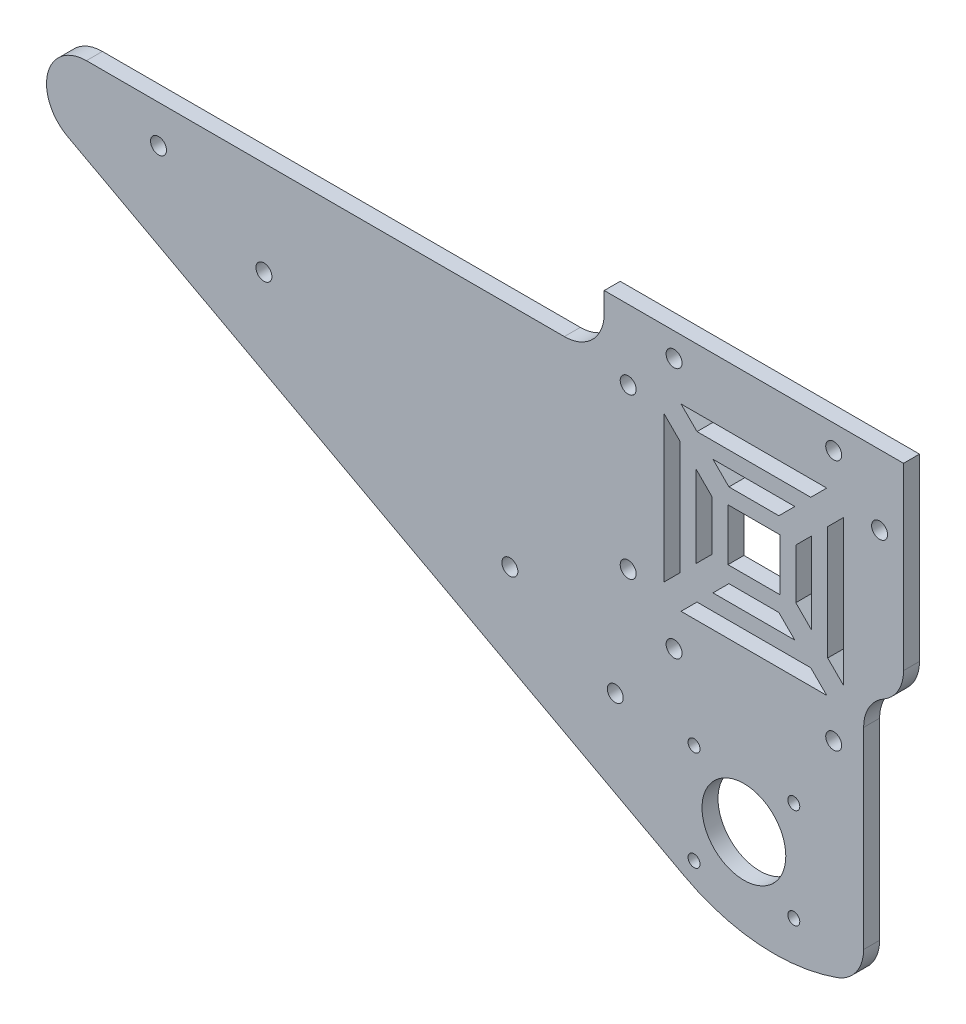
SolidWorks part; units mm, degrees
material "Thornel Mat VMA"
ref_plane "前视基准面" through (0, 0, 0) normal (0, 0, 1) x (1, 0, 0)
ref_plane "上视基准面" through (0, 0, 0) normal (0, 1, 0) x (1, 0, 0)
ref_plane "右视基准面" through (0, 0, 0) normal (1, 0, 0) x (0, 0, -1)
sketch "草图2" plane through (0, 0, 0) normal (0, 0, 1) x (1, 0, 0)
  line L0 (0, 0) -> (-75, 0)
  line L5 (-75, 0) -> (-75, -15)
  line L6 (-75, -15) -> (-244.4346, -15)
  line L7 (-244.4346, -15) -> (-55, -117)
  line L8 (-55, -117) -> (0, -117)
  line L9 (0, -117) -> (0, 0)
  dimension "D1" = 75
  dimension "D2" = 117
  dimension "D3" = 28.3
  dimension "D4" = 15
  dimension "D5" = 55
extrude "凸台-拉伸1" add sketch "草图2" along normal blind 4
sketch "草图3" plane through (0, 0, 4) normal (0, 0, 1) x (1, 0, 0)
  line L0 (-37.5, 0) -> (-37.5, -87.0707) construction
  line L1 (0, 0) -> (-75, 0) construction
  line L3 (-69, -17.5) -> (-6, -17.5) construction
  line L4 (-69, -17.5) -> (-69, -57.5) construction
  line L5 (-69, -57.5) -> (-6, -57.5) construction
  line L6 (-6, -17.5) -> (-6, -57.5) construction
  line L7 (-69, -17.5) -> (-6, -57.5) construction
  line L8 (-69, -57.5) -> (-6, -17.5) construction
  line L9 (-57.5, -6) -> (-17.5, -6) construction
  line L10 (-57.5, -6) -> (-57.5, -69) construction
  line L11 (-57.5, -69) -> (-17.5, -69) construction
  line L12 (-17.5, -6) -> (-17.5, -69) construction
  line L13 (-57.5, -6) -> (-17.5, -69) construction
  line L14 (-57.5, -69) -> (-17.5, -6) construction
  circle A0 centre (-57.5, -6) radius 2
  circle A1 centre (-69, -17.5) radius 2
  circle A2 centre (-17.5, -6) radius 2
  circle A3 centre (-6, -17.5) radius 2
  circle A4 centre (-6, -57.5) radius 2
  circle A5 centre (-17.5, -69) radius 2
  circle A6 centre (-57.5, -69) radius 2
  circle A7 centre (-69, -57.5) radius 2
  point P4 (-37.5, -37.5)
  point P9 (-37.5, -37.5)
  dimension "D6" = 4
  dimension "D1" = 63
  dimension "D2" = 40
  dimension "D3" = 37.5
  dimension "D4" = 40
  dimension "D5" = 63
extrude "切除-拉伸1" cut sketch "草图3" against normal through all
sketch "草图4" plane through (0, 0, 4) normal (0, 0, 1) x (1, 0, 0)
  line L0 (0, 0) -> (-75, 0) construction
  line L1 (0, -117) -> (0, 0) construction
  line L2 (-52.5, -87.5) -> (-27.5, -87.5) construction
  line L3 (-52.5, -87.5) -> (-52.5, -112.5) construction
  line L4 (-52.5, -112.5) -> (-27.5, -112.5) construction
  line L5 (-27.5, -87.5) -> (-27.5, -112.5) construction
  line L6 (-52.5, -87.5) -> (-27.5, -112.5) construction
  line L7 (-52.5, -112.5) -> (-27.5, -87.5) construction
  circle A0 centre (-40, -100) radius 10.5
  circle A1 centre (-52.5, -112.5) radius 1.5
  circle A2 centre (-27.5, -112.5) radius 1.5
  circle A3 centre (-27.5, -87.5) radius 1.5
  circle A4 centre (-52.5, -87.5) radius 1.5
  point P6 (-40, -100)
  dimension "D1" = 21
  dimension "D6" = 3
  dimension "D2" = 100
  dimension "D3" = 40
  dimension "D4" = 25
  dimension "D5" = 25
extrude "切除-拉伸2" cut sketch "草图4" against normal through all
sketch "草图5" plane through (0, 0, 4) normal (0, 0, 1) x (1, 0, 0)
  line L0 (-14.7555, -117) -> (-204.1901, -15) construction
  line L3 (-55, -117) -> (0, -117) construction
  line L4 (-75, -15) -> (-244.4346, -15) construction
  line L5 (-244.4346, -15) -> (-55, -117) construction
  line L6 (-40, -100) -> (-41.4223, -102.6414) construction
  circle A0 centre (-98.6533, -71.8257) radius 2
  circle A1 centre (-72.239, -86.0483) radius 2
  circle A2 centre (-160.2867, -38.6395) radius 2
  circle A3 centre (-186.701, -24.4169) radius 2
  point P7 (-40, -100)
  dimension "D2" = 4
  dimension "D3" = 30
  dimension "D5" = 30
  dimension "D1" = 3
  dimension "D4" = 35
  dimension "D6" = 100
extrude "切除-拉伸3" cut sketch "草图5" against normal through all
sketch "草图6" plane through (0, 0, 4) normal (0, 0, 1) x (1, 0, 0)
  line L1 (0, -117) -> (-10, -117)
  line L2 (0, -117) -> (0, -55)
  line L3 (0, -55) -> (-10, -55)
  line L4 (-10, -117) -> (-10, -55)
  dimension "D1" = 10
  dimension "D2" = 62
extrude "切除-拉伸4" cut sketch "草图6" against normal through all
fillet "圆角1" radius 10 1 edges at (0, -55, 2)
sketch "草图7" plane through (0, 0, 4) normal (0, 0, 1) x (1, 0, 0)
  line L0 (0, 0) -> (-75, 0) construction
  line L1 (-60, -15) -> (-15, -15)
  line L2 (-60, -15) -> (-60, -60)
  line L3 (-60, -60) -> (-15, -60)
  line L4 (-15, -15) -> (-15, -60)
  line L5 (-60, -15) -> (-15, -60) construction
  line L6 (-60, -60) -> (-15, -15) construction
  line L7 (0, -45) -> (0, 0) construction
  line L8 (-56, -19) -> (-56, -56)
  line L9 (-56, -56) -> (-19, -56)
  line L10 (-19, -19) -> (-19, -56)
  line L11 (-56, -19) -> (-19, -19)
  line L12 (-52, -23) -> (-52, -52)
  line L13 (-52, -52) -> (-23, -52)
  line L14 (-23, -23) -> (-23, -52)
  line L15 (-52, -23) -> (-23, -23)
  line L16 (-48, -27) -> (-48, -48)
  line L17 (-48, -48) -> (-27, -48)
  line L18 (-27, -27) -> (-27, -48)
  line L19 (-48, -27) -> (-27, -27)
  line L20 (-44, -31) -> (-31, -31)
  line L21 (-31, -31) -> (-31, -44)
  line L22 (-44, -44) -> (-31, -44)
  line L23 (-44, -31) -> (-44, -44)
  line L24 (-31.2426, -27) -> (-19.2426, -15)
  line L25 (-27, -31.2426) -> (-15, -19.2426)
  line L26 (-37.5, -15) -> (-37.5, -37.5) construction
  line L27 (-37.5, -37.5) -> (-15, -37.5) construction
  line L28 (-43.7574, -27) -> (-55.7574, -15)
  line L29 (-48, -31.2426) -> (-60, -19.2426)
  line L30 (-27, -43.7574) -> (-15, -55.7574)
  line L31 (-31.2426, -48) -> (-19.2426, -60)
  line L32 (-43.7574, -48) -> (-55.7574, -60)
  line L33 (-48, -43.7574) -> (-60, -55.7574)
  point P0 (-37.5, -37.5)
  dimension "D1" = 37.5
  dimension "D2" = 37.5
  dimension "D3" = 45
  dimension "D4" = 45
  dimension "D9" = 3
  dimension "D5" = 4
  dimension "D6" = 4
  dimension "D7" = 4
  dimension "D8" = 4
extrude "切除-拉伸5" cut sketch "草图7" against normal blind 4 contours L28 L11 L24 L1 | L33 L8 L29 L2 | L9 L32 L3 L31 | L10 L30 L4 L25 | L28 L19 L24 L15 | L33 L16 L29 L12 | L17 L32 L13 L31 | L18 L30 L14 L25 | L20 L23 L22 L21 region at (-37.5, -16.918, 4) region at (-58.082, -37.5, 4) region at (-37.5, -24.8385, 4) region at (-50.1615, -37.5, 4) region at (-16.918, -37.5, 4) region at (-37.5, -58.082, 4) region at (-24.8385, -37.5, 4) region at (-37.5, -50.1615, 4) region at (-37.5, -37.5, 4)
sketch "草图8" plane through (0, 0, 4) normal (0, 0, 1) x (1, 0, 0)
  line L0 (-244.4346, -15) -> (-55, -117) construction
  line L3 (-55, -117) -> (-10, -117)
  circle A0 centre (-32.5, -75.213) radius 47.4595
extrude "凸台-拉伸2" add sketch "草图8" against normal up to surface (4 mm away) contours L3 A0 region at (-32.5, -119.281, 4) up to face at (-50, -37.5, 0)
fillet "圆角2" radius 10 4 edges at (-10, -55, 2) (-244.4346, -15, 2) (-75, -15, 2) (-10, -117, 2)
